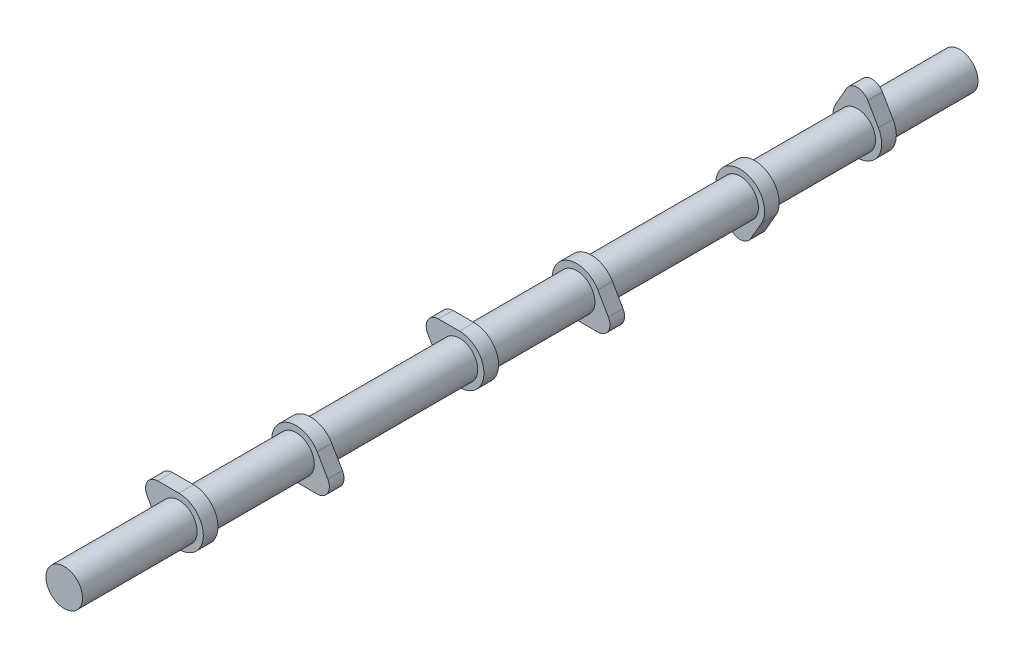
SolidWorks part; units mm, degrees
ref_plane "Front Plane" through (0, 0, 0) normal (0, 0, 1) x (1, 0, 0)
ref_plane "Top Plane" through (0, 0, 0) normal (0, 1, 0) x (1, 0, 0)
ref_plane "Right Plane" through (0, 0, 0) normal (1, 0, 0) x (0, 0, -1)
sketch "Sketch1" plane through (0, 0, 0) normal (0, 0, 1) x (1, 0, 0)
  line L0 (-5.4993, 15.875) -> (-10.9985, 6.35)
  line L1 (5.4993, 15.875) -> (10.9985, 6.35)
  arc A0 (-10.9985, 6.35) -> (10.9985, 6.35) centre (0, 0) ccw
  arc A1 (5.4993, 15.875) -> (-5.4993, 15.875) centre (0, 12.7) ccw
  dimension "D1" = 25.4
  dimension "D2" = 12.7
  dimension "D3" = 12.7
  dimension "D4" = 12.7
extrude "Boss-Extrude1" add sketch "Sketch1" along normal mid plane 7.62
ref_axis "Axis1" through (0, 0, 106.8082) along (0, 0, -1)
move or copy body "Body-Move/Copy1" bodies to move or copy 101 copy yes number of copies 1 translate (0, 0, 60.96) parameters "D1"=0, "D2"=0, "D3"=0
move or copy body "Body-Move/Copy2" bodies to move or copy 102 copy no rotation origin (0, 0, 0) rotation axis (0, 0, 1) rotation angle 180
sketch "Sketch2" plane through (0, 0, 3.81) normal (0, 0, 1) x (1, 0, 0)
  circle A0 centre (0, 0) radius 9.5
  dimension "D1" = 19
extrude "Boss-Extrude3" add sketch "Sketch2" along direction (0, 0, -1) on the side of the normal blind 146.05 from offset 25.4 separate body offset against normal yes
pattern_linear "LPattern1" count 3 spacing 146.05 along (0, 0, 1) of bodies 104 101 103
move or copy body "Body-Move/Copy3" bodies to move or copy 109 107 copy no rotation origin (0, 0, 0) rotation axis (0, 0, -1) rotation angle 120
move or copy body "Body-Move/Copy4" bodies to move or copy 106 110 108 copy no rotation origin (0, 0, 0) rotation axis (0, 0, -1) rotation angle 120
combine bodies "Combine1" operation type add bodies to combine 104 117 114 115 105 101 103 116 113
other "Move Face1" face at (9.5, 0, -21.59) offset 27.94 parameters "D1"=27.94
ref_plane "Plane1" through (8.6168, 9.3295, 0) normal (0.6785, 0.7346, 0) x (0, 0, 1)
